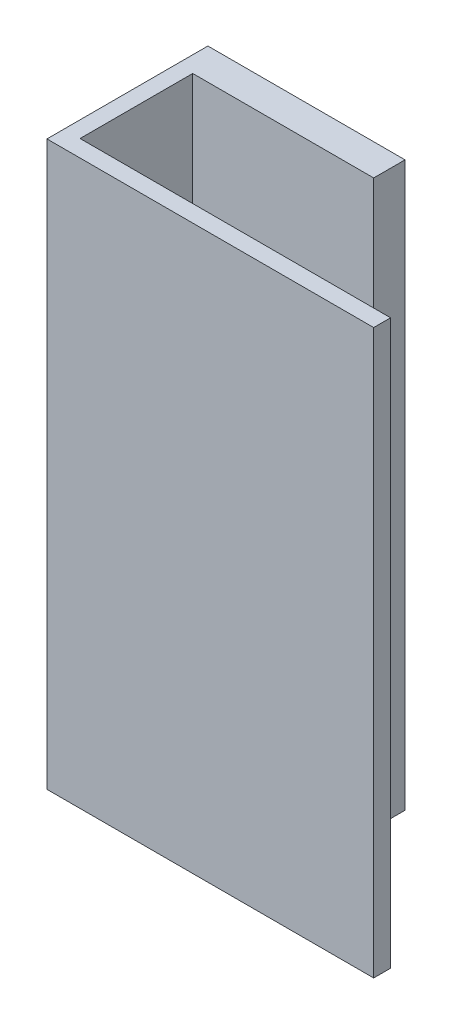
SolidWorks part; units mm, degrees
ref_plane "Front Plane" through (0, 0, 0) normal (0, 0, 1) x (1, 0, 0)
ref_plane "Top Plane" through (0, 0, 0) normal (0, 1, 0) x (1, 0, 0)
ref_plane "Right Plane" through (0, 0, 0) normal (1, 0, 0) x (0, 0, -1)
sketch "Sketch2" plane through (0, 0, 0) normal (0, 1, 0) x (1, 0, 0)
  line L1 (0, 0) -> (106, 0)
  line L2 (0, 0) -> (0, 106)
  line L3 (0, 106) -> (106, 106)
  line L4 (106, 0) -> (106, 106)
  circle A0 centre (18, 15) radius 4
  circle A1 centre (92, 13.5) radius 6
  dimension "D3" = 8
  dimension "D4" = 12
  dimension "D5" = 15
  dimension "D6" = 18
  dimension "D7" = 13.5
  dimension "D8" = 14
  dimension "D1" = 106
  dimension "D2" = 106
extrude "Boss-Extrude1" add sketch "Sketch2" along normal blind 25
sketch "Sketch3" plane through (0, 25, 0) normal (0, 1, 0) x (1, 0, 0)
  line L0 (3, 103) -> (3, 3)
  line L1 (0, 106) -> (106, 106)
  line L2 (0, 106) -> (0, 0)
  line L3 (0, 0) -> (106, 0)
  line L4 (106, 106) -> (106, 0)
  line L5 (3, 3) -> (103, 3)
  line L6 (103, 103) -> (103, 3)
  line L7 (3, 103) -> (103, 103)
  dimension "D1" = 3
extrude "Boss-Extrude2" add sketch "Sketch3" along normal blind 20
sketch "Sketch5" plane through (0, 25, 0) normal (0, 1, 0) x (1, 0, 0)
  line L0 (3, 103) -> (3, 3) construction
  line L2 (3, 28) -> (3, 25)
  line L5 (3, 103) -> (3, 3) construction
  line L6 (83, 52.5) -> (83, 26.5)
  line L9 (32, 43) -> (35, 43)
  line L10 (35, 23) -> (35, 43)
  line L12 (3, 63) -> (3, 60)
  line L19 (22, 63) -> (22, 80)
  line L20 (3, 3) -> (103, 3) construction
  line L21 (58, 3) -> (61, 3)
  line L22 (58, 3) -> (58, 26)
  line L23 (58, 26) -> (61, 26)
  line L24 (61, 3) -> (61, 26)
  line L25 (3, 28) -> (32, 28)
  line L26 (3, 3) -> (103, 3) construction
  line L27 (73, 3) -> (76, 3)
  line L30 (76, 3) -> (76, 26.5)
  line L38 (80, 29.5) -> (80, 49.5)
  line L41 (80, 49.5) -> (73, 49.5)
  line L42 (73, 52.5) -> (73, 49.5)
  line L44 (76, 26.5) -> (83, 26.5)
  line L45 (73, 52.5) -> (83, 52.5)
  line L47 (3, 63) -> (22, 63)
  line L50 (80, 29.5) -> (73, 29.5)
  line L51 (73, 29.5) -> (73, 3)
  line L52 (25, 60) -> (3, 60)
  line L53 (25, 60) -> (25, 80)
  line L54 (25, 80) -> (22, 80)
  line L55 (32, 43) -> (32, 28)
  line L56 (3, 25) -> (32, 25)
  line L57 (32, 25) -> (32, 23)
  line L58 (32, 23) -> (35, 23)
  dimension "D1" = 22
  dimension "D2" = 19
  dimension "D3" = 0
  dimension "D4" = 29
  dimension "D5" = 29
  dimension "D6" = 55
  dimension "D7" = 58
extrude "Boss-Extrude3" add sketch "Sketch5" along normal blind 20 contours L9 L10 L58 L57 L56 L2 L25 L55 | L54 L19 L47 L12 L52 L53 | L22 L21 L24 L23 | L51 L27 L30 L44 L6 L45 L42 L41 L38 L50
sketch "Sketch7" plane through (0, 25, 0) normal (0, 1, 0) x (1, 0, 0)
  line L1 (73, 52.5) -> (76, 52.5)
  line L2 (73, 52.5) -> (73, 82.5)
  line L3 (73, 82.5) -> (76, 82.5)
  line L4 (76, 52.5) -> (76, 82.5)
  line L5 (73, 73.4965) -> (53, 73.4965)
  line L6 (73, 73.4965) -> (73, 70.4965)
  line L7 (73, 70.4965) -> (53, 70.4965)
  line L8 (53, 73.4965) -> (53, 70.4965)
  line L9 (53, 70.4965) -> (50, 70.4965)
  line L10 (53, 70.4965) -> (53, 83.4965)
  line L11 (53, 83.4965) -> (50, 83.4965)
  line L12 (50, 70.4965) -> (50, 83.4965)
  line M14 (73, 52.5) -> (83, 52.5)
  dimension "D1" = 3
  dimension "D2" = 3
  dimension "D3" = 3
  dimension "D4" = 30
  dimension "D5" = 20
  dimension "D6" = 13
extrude "Boss-Extrude4" add sketch "Sketch7" along normal blind 20 contours L12 L9 L8 L10 L11 | L5 L8 L7 L2 | L4 L3 L2 M14 region at (74.5, 25, -67.5) region at (63, 25, -71.9965) region at (51.5, 25, -76.9965)
sketch "Sketch9" plane through (0, 25, 0) normal (0, 1, 0) x (1, 0, 0)
  circle A0 centre (92, 13.5) radius 9.9058
extrude "Cut-Extrude1" cut sketch "Sketch9" against normal blind 10
fillet "Fillet1" [suppressed] radius 5
sketch "Sketch10" plane through (0, 0, 0) normal (0, 0, 1) x (1, 0, 0)
  line L0 (0, 0) -> (106, 0) construction
  line L1 (48, 4) -> (58, 4)
  line L2 (48, 4) -> (48, 0)
  line L3 (48, 0) -> (58, 0)
  line L4 (58, 4) -> (58, 0)
  line L5 (0, 45) -> (106, 45) construction
  point P6 (53, 4)
  point P9 (53, 45)
  dimension "D1" = 10
  dimension "D2" = 4
  dimension "D3" = 0
  dimension "D4" = 0
extrude "Boss-Extrude5" add sketch "Sketch10" along normal blind 10
sketch "Sketch11" plane through (0, 0, -106) normal (0, 0, -1) x (-1, 0, 0)
  line L0 (-106, 45) -> (0, 45) construction
  line L1 (-58, 4) -> (-48, 4)
  line L2 (-58, 4) -> (-58, 0)
  line L3 (-58, 0) -> (-48, 0)
  line L4 (-48, 4) -> (-48, 0)
  line L5 (-106, 0) -> (0, 0) construction
  point P4 (-53, 4)
  point P7 (-53, 45)
  dimension "D1" = 10
  dimension "D2" = 4
  dimension "D3" = 0
  dimension "D4" = 0
extrude "Boss-Extrude6" add sketch "Sketch11" along normal blind 10
fillet "Fillet2" 2 edges at (48, 2, -116) (58, 2, -116) type full round first side face at (48, 2, -111) second side face at (58, 2, -111) middle face at (53, 2, -116)
fillet "Fillet3" radius 5 2 edges at (48, 2, -106) (58, 2, -106)
fillet "Fillet4" radius 5 2 edges at (48, 2, 0) (58, 2, 0)
fillet "Fillet5" 2 edges at (48, 2, 10) (58, 2, 10) type full round first side face at (48, 2, 7.5) second side face at (58, 2, 7.5) middle face at (53, 2, 10)
sketch "Sketch13" plane through (0, 4, 0) normal (0, 1, 0) x (1, 0, 0)
  circle A0 centre (53, -5) radius 1.6
  circle A1 centre (53, 111) radius 1.6
  dimension "D1" = 3.2
  dimension "D2" = 3.2
extrude "Cut-Extrude2" cut sketch "Sketch13" against normal through all
sketch "Sketch14" plane through (0, 0, 0) normal (0, 0, 1) x (1, 0, 0)
  line L1 (106, 0) -> (70.0395, 0)
  line L2 (106, 0) -> (106, 7.6935)
  line L3 (106, 7.6935) -> (70.0395, 7.6935)
  line L4 (70.0395, 0) -> (70.0395, 7.6935)
extrude "Cut-Extrude3" cut sketch "Sketch14" against normal blind 30
sketch "Sketch15" plane through (0, 45, 0) normal (0, 1, 0) x (1, 0, 0)
  line L0 (0, 106) -> (0, 0) construction
  line L1 (0, 28.5668) -> (2.8761, 28.5668)
  line L2 (0, 28.5668) -> (0, 0)
  line L3 (0, 0) -> (2.8761, 0)
  line L4 (2.8761, 23) -> (2.8761, 3)
  line L5 (0, 0) -> (106, 0) construction
  line L7 (58, 3) -> (2.8761, 3)
  line L8 (58, 3) -> (58, 0)
  line L9 (58, 0) -> (2.8761, 0)
  line L11 (0, 28.5668) -> (35, 28.5668)
  line L12 (0, 28.5668) -> (0, 23)
  line L13 (2.8761, 23) -> (35, 23)
  line L14 (35, 28.5668) -> (35, 23)
extrude "Boss-Extrude7" add sketch "Sketch15" along normal blind 100 contours L11 L14 L13 L4 L7 L8 L9 L3 L2
sketch "Sketch21" plane through (0, 45, 0) normal (0, 1, 0) x (1, 0, 0)
  line L1 (-23.8926, 119.4726) -> (127.5571, 119.4726)
  line L2 (-23.8926, 119.4726) -> (-23.8926, -15.2691)
  line L3 (-23.8926, -15.2691) -> (127.5571, -15.2691)
  line L4 (127.5571, 119.4726) -> (127.5571, -15.2691)
extrude "Cut-Extrude6" cut sketch "Sketch21" against normal through all
